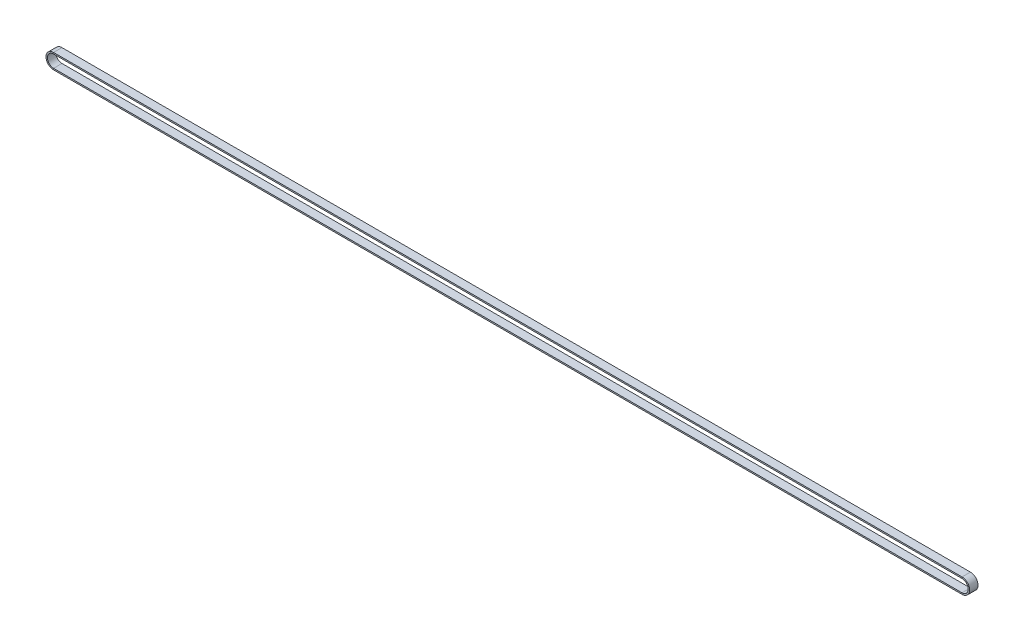
SolidWorks part; units mm, degrees
ref_plane "Front Plane" through (0, 0, 0) normal (0, 0, 1) x (1, 0, 0)
ref_plane "Top Plane" through (0, 0, 0) normal (0, 1, 0) x (1, 0, 0)
ref_plane "Right Plane" through (0, 0, 0) normal (1, 0, 0) x (0, 0, -1)
sketch "Sketch2" plane through (0, 0, 0) normal (0, 0, 1) x (1, 0, 0)
  line L0 (0, 0) -> (1, 0) construction
  line L1 (0, 0) -> (0, 1) construction
  line L2 (-0.0001, 41.109) -> (-976.331, 41.109)
  line L3 (-976.331, 57.3885) -> (-0.0001, 57.3885)
  arc A0 (-0.0001, 57.3885) -> (-0.0001, 41.109) centre (-0.0001, 49.2488) cw
  arc A1 (-976.331, 41.109) -> (-976.331, 57.3885) centre (-976.331, 49.2488) cw
ref_plane "Plane1" through (-0.0001, 57.3885, 0) normal (1, 0, 0) x (0, 0, -1)
sketch "Sketch3" plane through (-0.0001, 57.3885, 0) normal (1, 0, 0) x (0, 0, -1)
  line L1 (0, -1.5) -> (9, -1.5)
  line L2 (0, -1.5) -> (0, 0)
  line L3 (0, 0) -> (9, 0)
  line L4 (9, -1.5) -> (9, 0)
  dimension "D1" = 1.5
  dimension "D2" = 9
sweep "Sweep1" add profiles "Sketch3" path "Sketch2"
